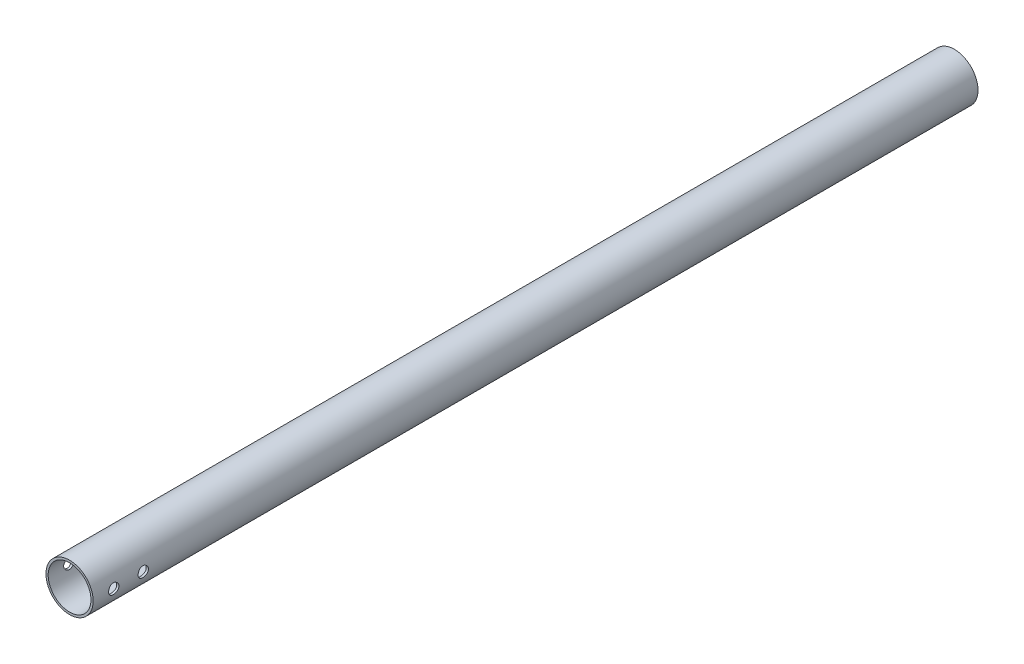
SolidWorks part; units mm, degrees
ref_plane "Plano frontal" through (0, 0, 0) normal (0, 0, 1) x (1, 0, 0)
ref_plane "Plano superior" through (0, 0, 0) normal (0, 1, 0) x (1, 0, 0)
ref_plane "Plano direito" through (0, 0, 0) normal (1, 0, 0) x (0, 0, -1)
sketch "Esboço1" plane through (0, 0, 0) normal (0, 0, 1) x (1, 0, 0)
  circle A0 centre (0, 0) radius 7.25
  circle A1 centre (0, 0) radius 8
  dimension "D1" = 16
  dimension "D2" = 14.5
extrude "Ressalto-extrusão1" add sketch "Esboço1" along normal blind 300
sketch "Esboço2" plane through (0, 0, 0) normal (1, 0, 0) x (0, 0, -1)
  line L0 (55, 0) -> (-55, 0) construction
  line L1 (-300, 8) -> (-300, -8) construction
  line L2 (-300, 8) -> (-300, -8) construction
  line L3 (-300, 0) -> (-269.1098, 0) construction
  circle A0 centre (-293, 0) radius 1.75
  circle A1 centre (-283, 0) radius 1.75
  dimension "D2" = 3.5
  dimension "D3" = 7
  dimension "D4" = 10
extrude "Corte-extrusão1" cut sketch "Esboço2" against normal blind 300 and the other way blind 300
sketch "Sketch2" plane through (0, 0, 0) normal (0, 1, 0) x (1, 0, 0)
  line L0 (-8, -300) -> (8, -300) construction
  line L1 (0, -300) -> (0, 0) construction
  circle A0 centre (0, -147) radius 3.5
  dimension "D1" = 7
  dimension "D2" = 153
extrude "Cut-Extrude1" cut sketch "Sketch2" against normal up to next
